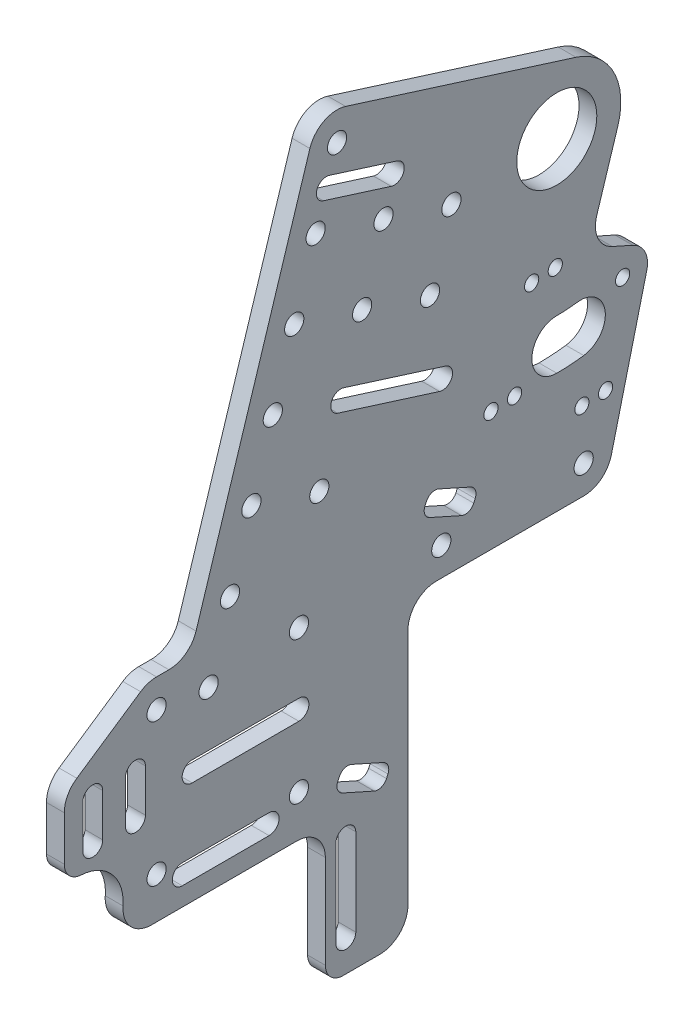
SolidWorks part; units mm, degrees
ref_plane "Front Plane" through (0, 0, 0) normal (0, 0, 1) x (1, 0, 0)
ref_plane "Top Plane" through (0, 0, 0) normal (0, 1, 0) x (1, 0, 0)
ref_plane "Right Plane" through (0, 0, 0) normal (1, 0, 0) x (0, 0, -1)
sketch "Sketch2" plane through (0, 0, 0) normal (1, 0, 0) x (0, 0, -1)
  line L3 (119.2424, 0) -> (-119.2424, 0) construction
  line L9 (71.2451, 111.4062) -> (68.2175, 112.7608) construction
  line L28 (0, 0) -> (-57.2178, 40.0643) construction
  line L40 (0, 0) -> (113.3671, 198.5091) construction
  line L41 (113.3671, 198.5091) -> (58.7631, 215.7257) construction
  line L42 (99.338, 182.3162) -> (24.13, 14.224) construction
  line L43 (35.7423, 40.1778) -> (35.2236, 39.0185) construction
  line L44 (30.078, 221.0415) -> (54.3024, 213.4035)
  line L45 (32.2166, 227.8243) -> (56.441, 220.1864)
  line L46 (40.1245, 41.8508) -> (51.4581, 36.7799)
  line L47 (53.1311, 32.3976) -> (52.6124, 31.2384)
  line L48 (48.2302, 29.5654) -> (36.8966, 34.6363)
  line L49 (104.399, 158.5001) -> (136.8581, 143.9772) construction
  line L50 (136.8581, 143.9772) -> (122.3352, 111.518) construction
  line L51 (112.8406, 159.0638) -> (145.2997, 144.5408) construction
  line L52 (66.8628, 109.7332) -> (66.3442, 108.5739)
  line L53 (71.2451, 111.4062) -> (82.5787, 106.3353)
  line L54 (84.2517, 101.953) -> (83.733, 100.7938)
  line L55 (79.3508, 99.1208) -> (68.0172, 104.1917)
  line L56 (43.9148, 180.4584) -> (36.2769, 156.2339) construction
  line L57 (-29.4365, 93.5262) -> (-29.4365, 42.7262) construction
  line L61 (122.3352, 111.518) -> (89.876, 126.041) construction
  line L62 (89.876, 126.041) -> (104.399, 158.5001) construction
  line L63 (104.399, 158.5001) -> (122.3352, 111.518) construction
  line L65 (145.2997, 144.5408) -> (130.7768, 112.0817) construction
  line L66 (130.7768, 112.0817) -> (98.3176, 126.6046) construction
  line L67 (98.3176, 126.6046) -> (112.8406, 159.0638) construction
  line L68 (112.8406, 159.0638) -> (130.7768, 112.0817) construction
  line L69 (58.7631, 215.7257) -> (31.1473, 224.4329) construction
  line L70 (40.1245, 41.8508) -> (37.0969, 43.2054) construction
  line L71 (38.1, 20.2565) -> (38.1, -10.7315) construction
  line L72 (41.656, 20.2565) -> (41.656, -10.7315)
  line L73 (34.544, 20.2565) -> (34.544, -10.7315)
  line L74 (0, -14.2875) -> (38.1, -14.2875) construction
  line L75 (-20.2565, 38.1) -> (10.7315, 38.1) construction
  line L76 (-20.2565, 41.656) -> (10.7315, 41.656)
  line L77 (-20.2565, 34.544) -> (10.7315, 34.544)
  line L78 (14.2875, 38.1) -> (14.2875, 0) construction
  line L79 (-52.2013, 78.1643) -> (-52.2013, 62.9243) construction
  line L80 (-48.6453, 78.1643) -> (-48.6453, 62.9243)
  line L81 (-55.7573, 78.1643) -> (-55.7573, 62.9243)
  line L82 (-36.9613, 78.1643) -> (-36.9613, 62.9243) construction
  line L83 (-33.4053, 78.1643) -> (-33.4053, 62.9243)
  line L84 (-40.5173, 78.1643) -> (-40.5173, 62.9243)
  line L85 (31.1473, 224.4329) -> (-10.8613, 91.1986) construction
  line L86 (31.1473, 224.4329) -> (34.9663, 236.5451) construction
  line L87 (35.7423, 40.1778) -> (35.2236, 39.0185)
  line L92 (27.3284, 212.3207) -> (75.7772, 197.0448) construction
  line L93 (19.6904, 188.0963) -> (68.1392, 172.8204) construction
  line L94 (36.2769, 156.2339) -> (12.0525, 163.8719) construction
  line L95 (36.2769, 156.2339) -> (72.6135, 144.777) construction
  line L96 (37.3462, 159.6254) -> (73.6828, 148.1685)
  line L97 (35.2076, 152.8425) -> (71.5442, 141.3856)
  line L98 (36.2769, 156.2339) -> (28.639, 132.0095) construction
  line L99 (28.639, 132.0095) -> (4.4146, 139.6475) construction
  line L100 (-29.4365, 68.1262) -> (-16.7365, 68.1262) construction
  line L101 (-16.7365, 68.1262) -> (21.3635, 68.1262) construction
  line L102 (-16.7365, 71.6822) -> (21.3635, 71.6822)
  line L103 (-16.7365, 64.5702) -> (21.3635, 64.5702)
  line L104 (38.0214, 246.2349) -> (120.2412, 220.3111)
  line L105 (25.2765, 239.6003) -> (-15.3369, 110.7911)
  line L106 (-29.4365, 103.6862) -> (-25.0266, 103.6862)
  line L107 (-35.1197, 101.9481) -> (-57.8844, 86.5862)
  line L108 (-62.3613, 62.2565) -> (-62.3613, 78.1643)
  line L109 (-31.257, 27.94) -> (20.6375, 27.94)
  line L110 (30.7975, -15.5575) -> (30.7975, 17.78)
  line L111 (37.1475, -21.9075) -> (50.1035, -21.9075)
  line L112 (60.2635, 73.2062) -> (60.2635, -11.7475)
  line L113 (135.1691, 191.635) -> (127.6222, 167.6992)
  line L114 (133.1625, 155.37) -> (140.4889, 152.092)
  line L115 (145.4838, 141.8254) -> (132.8214, 91.067)
  line L116 (122.9635, 83.3662) -> (70.4235, 83.3662)
  circle A36 centre (0, 0) radius 14.2875 construction
  circle A37 centre (-57.2178, 40.0643) radius 14.2875 construction
  circle A38 centre (113.3671, 198.5091) radius 14.2875
  arc A39 (54.3024, 213.4035) -> (56.441, 220.1864) centre (55.3717, 216.795) ccw
  arc A40 (32.2166, 227.8243) -> (30.078, 221.0415) centre (31.1473, 224.4329) ccw
  arc A41 (51.4581, 36.7799) -> (53.1311, 32.3976) centre (50.1035, 33.7523) cw
  arc A42 (52.6124, 31.2384) -> (48.2302, 29.5654) centre (49.5848, 32.593) cw
  arc A43 (36.8966, 34.6363) -> (35.2236, 39.0185) centre (38.2512, 37.6639) cw
  arc A44 (35.7423, 40.1778) -> (40.1245, 41.8508) centre (38.7699, 38.8232) cw
  arc A45 (79.3508, 99.1208) -> (83.733, 100.7938) centre (80.7054, 102.1484) ccw
  arc A46 (84.2517, 101.953) -> (82.5787, 106.3353) centre (81.2241, 103.3077) ccw
  arc A47 (68.0172, 104.1917) -> (66.3442, 108.5739) centre (69.3718, 107.2193) cw
  arc A48 (66.8628, 109.7332) -> (71.2451, 111.4062) centre (69.8905, 108.3785) cw
  circle A49 centre (-29.4365, 42.7262) radius 3.429
  circle A50 centre (21.3635, 93.5262) radius 3.429
  circle A51 centre (122.9635, 93.5262) radius 3.429
  circle A54 centre (104.399, 158.5001) radius 2.54
  circle A55 centre (136.8581, 143.9772) radius 2.54
  circle A56 centre (122.3352, 111.518) radius 2.54
  circle A57 centre (89.876, 126.041) radius 2.54
  arc A60 (113.3671, 135.0091) -> (121.8087, 135.5727) centre (113.3671, 198.5091) ccw construction
  circle A61 centre (112.8406, 159.0638) radius 2.54
  circle A62 centre (130.7768, 112.0817) radius 2.54
  circle A63 centre (98.3176, 126.6046) radius 2.54
  circle A64 centre (-29.4365, 93.5262) radius 3.429
  circle A65 centre (21.3635, 42.7262) radius 3.429
  circle A66 centre (72.1635, 93.5262) radius 3.429
  arc A67 (41.656, 20.2565) -> (34.544, 20.2565) centre (38.1, 20.2565) ccw
  arc A68 (34.544, -10.7315) -> (41.656, -10.7315) centre (38.1, -10.7315) ccw
  arc A69 (-20.2565, 41.656) -> (-20.2565, 34.544) centre (-20.2565, 38.1) ccw
  arc A70 (10.7315, 34.544) -> (10.7315, 41.656) centre (10.7315, 38.1) ccw
  arc A71 (-48.6453, 78.1643) -> (-55.7573, 78.1643) centre (-52.2013, 78.1643) ccw
  arc A72 (-55.7573, 62.9243) -> (-48.6453, 62.9243) centre (-52.2013, 62.9243) ccw
  arc A73 (-33.4053, 78.1643) -> (-40.5173, 78.1643) centre (-36.9613, 78.1643) ccw
  arc A74 (-40.5173, 62.9243) -> (-33.4053, 62.9243) centre (-36.9613, 62.9243) ccw
  circle A75 centre (34.9663, 236.5451) radius 3.429
  circle A76 centre (27.3284, 212.3207) radius 3.429
  circle A77 centre (19.6904, 188.0963) radius 3.429
  circle A78 centre (12.0525, 163.8719) radius 3.429
  circle A79 centre (4.4146, 139.6475) radius 3.429
  circle A80 centre (-3.2234, 115.423) radius 3.429
  circle A81 centre (-10.8613, 91.1986) radius 3.429
  circle A82 centre (51.5528, 204.6828) radius 3.429
  circle A83 centre (43.9148, 180.4584) radius 3.429
  circle A84 centre (75.7772, 197.0448) radius 3.429
  circle A85 centre (68.1392, 172.8204) radius 3.429
  arc A86 (37.3462, 159.6254) -> (35.2076, 152.8425) centre (36.2769, 156.2339) ccw
  arc A87 (71.5442, 141.3856) -> (73.6828, 148.1685) centre (72.6135, 144.777) ccw
  circle A88 centre (28.639, 132.0095) radius 3.429
  arc A89 (-16.7365, 71.6822) -> (-16.7365, 64.5702) centre (-16.7365, 68.1262) ccw
  arc A90 (21.3635, 64.5702) -> (21.3635, 71.6822) centre (21.3635, 68.1262) ccw
  arc A91 (38.0214, 246.2349) -> (25.2765, 239.6003) centre (34.9663, 236.5451) ccw
  arc A92 (120.2412, 220.3111) -> (135.1691, 191.635) centre (113.3671, 198.5091) cw
  arc A93 (-35.1197, 101.9481) -> (-29.4365, 103.6862) centre (-29.4365, 93.5262) cw
  arc A94 (-62.3613, 78.1643) -> (-57.8844, 86.5862) centre (-52.2013, 78.1643) cw
  arc A95 (-25.0266, 103.6862) -> (-15.3369, 110.7911) centre (-25.0266, 113.8462) ccw
  arc A96 (-56.356, 55.9159) -> (-62.3613, 62.2565) centre (-56.0113, 62.2565) cw
  arc A97 (-41.388, 38.8666) -> (-56.356, 55.9159) centre (-57.2178, 40.0643) ccw
  arc A98 (20.6375, 27.94) -> (30.7975, 17.78) centre (20.6375, 17.78) cw
  arc A99 (-31.257, 27.94) -> (-41.388, 38.8666) centre (-31.257, 38.1) cw
  arc A100 (37.1475, -21.9075) -> (30.7975, -15.5575) centre (37.1475, -15.5575) cw
  arc A101 (140.4889, 152.092) -> (145.4838, 141.8254) centre (136.8581, 143.9772) cw
  arc A102 (132.8214, 91.067) -> (122.9635, 83.3662) centre (122.9635, 93.5262) cw
  arc A103 (50.1035, -21.9075) -> (60.2635, -11.7475) centre (50.1035, -11.7475) ccw
  arc A104 (60.2635, 73.2062) -> (70.4235, 83.3662) centre (70.4235, 73.2062) cw
  arc A105 (133.1625, 155.37) -> (127.6222, 167.6992) centre (137.3119, 164.644) cw
  arc A106 (121.8087, 135.5727) -> (113.3671, 135.0091) centre (113.3671, 198.5091) cw construction
  arc A107 (113.3671, 126.1191) -> (122.9905, 126.7616) centre (113.3671, 198.5091) ccw
  arc A108 (113.3671, 143.8991) -> (120.6269, 144.3838) centre (113.3671, 198.5091) ccw
  arc A109 (113.3671, 143.8991) -> (113.3671, 126.1191) centre (113.3671, 135.0091) ccw
  arc A110 (122.9905, 126.7616) -> (120.6269, 144.3838) centre (121.8087, 135.5727) ccw
  point P31 (113.3671, 135.0091)
  point P37 (2.3135, 68.1262)
  point P70 (54.4452, 150.5055)
  point P80 (121.8087, 135.5727)
  point P89 (38.1, 4.7625)
  point P98 (-4.7625, 38.1)
  point P100 (38.1, 23.8125)
  point P109 (-23.8125, 38.1)
  point P111 (-52.2013, 70.5443)
  point P116 (-36.9613, 70.5443)
  point P176 (117.5973, 135.1502)
  point P192 (0, 0)
  dimension "D1" = 28.575
  dimension "D2" = 69.85
  dimension "D5" = 25.4
  dimension "D6" = 3.556
  dimension "D7" = 184.15
  dimension "D8" = 28.0103
  dimension "D9" = 3.3168
  dimension "D10" = 10.16
  dimension "D11" = 27.7812
  dimension "D13" = 6.858
  dimension "D15" = 53.4619
  dimension "D17" = 180.1812
  dimension "D18" = 53.4619
  dimension "D19" = 3.556
  dimension "D20" = 38.1
  dimension "D21" = 38.1
  dimension "D24" = 5.08
  dimension "D28" = 10.16
  dimension "D30" = 35.56
  dimension "D31" = 8.4416
  dimension "D33" = 65.895
  dimension "D34" = 35
  dimension "D35" = 60.27
  dimension "D40" = 76.2
  dimension "D16" = 6.858
  dimension "D27" = 10.16
  dimension "D47" = 38.1
  dimension "D48" = 7.112
  dimension "D50" = 38.1
  dimension "D53" = 3.556
  dimension "D56" = 12.7
  dimension "D57" = 12.7
  dimension "D58" = 25.4
  dimension "D60" = 25.4
  dimension "D61" = 25.4
  dimension "D25" = 3.556
  dimension "D63" = 6.35
  dimension "D64" = 31.75
  dimension "D65" = 10.16
  dimension "D69" = 16.51
  dimension "D70" = 11.176
  dimension "D73" = 6.35
  dimension "D74" = 10.16
  dimension "D72" = 8.89
  dimension "D75" = 8.89
  dimension "D77" = 7.2813
  dimension "D3" = 228.6
  dimension "D12" = 2.6619
  dimension "D14" = 78.5812
  dimension "D22" = 35.56
  dimension "D23" = 63.5
  dimension "D26" = 12.7
  dimension "D29" = 8.4667
  dimension "D32" = 50.8
  dimension "D36" = 16.1929
  dimension "D37" = 12.4163
  dimension "D38" = 1.27
  dimension "D39" = 76.2
  dimension "D41" = 1.27
  dimension "D42" = 12.4163
  dimension "D43" = 17.5
  dimension "D44" = 7.112
  dimension "D45" = 3.556
  dimension "D46" = 38.1
  dimension "D49" = 38.1
  dimension "D51" = 15.24
  dimension "D52" = 15.24
  dimension "D54" = 38.1
  dimension "D55" = 23.8125
  dimension "D59" = 25.4
  dimension "D62" = 25.4
  dimension "D66" = 15.494
  dimension "D67" = 3
  dimension "D68" = 25.4
  dimension "D71" = 7.62
  dimension "D76" = 60.8098
extrude "Boss-Extrude1" add sketch "Sketch2" along normal blind 3.175 and the other way blind 3.175
